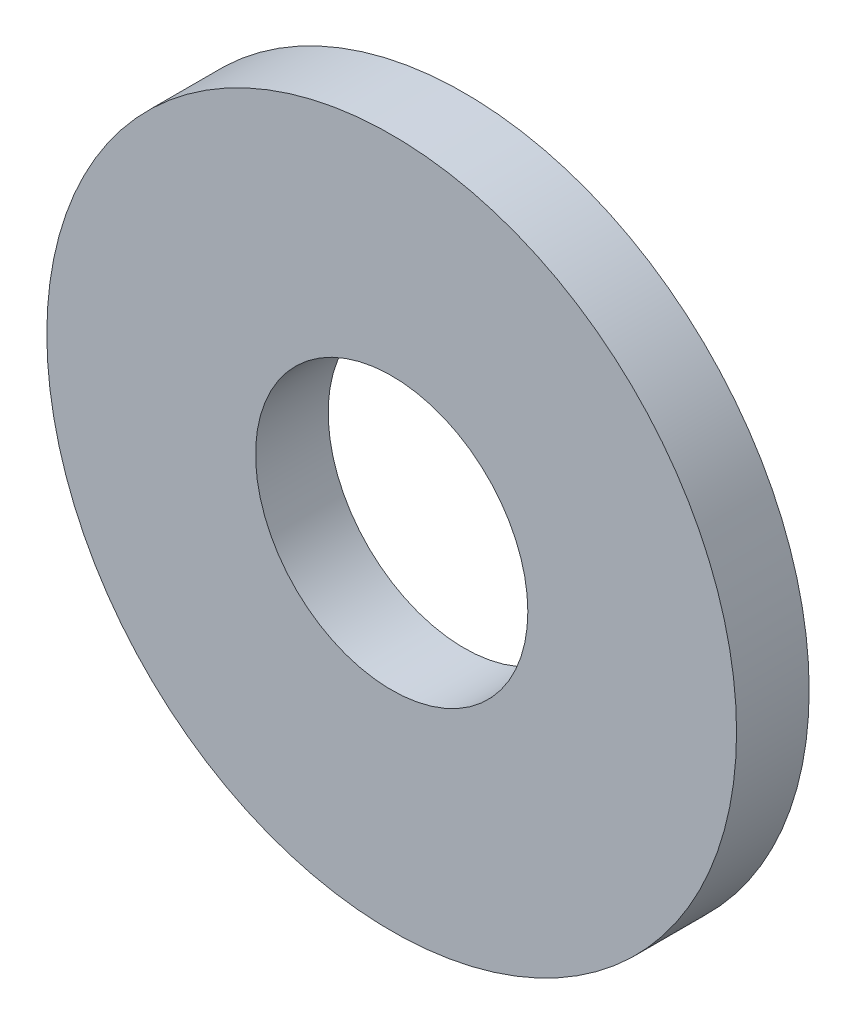
SolidWorks part; units mm, degrees
ref_plane "Front Plane" through (0, 0, 0) normal (0, 0, 1) x (1, 0, 0)
ref_plane "Top Plane" through (0, 0, 0) normal (0, 1, 0) x (1, 0, 0)
ref_plane "Right Plane" through (0, 0, 0) normal (1, 0, 0) x (0, 0, -1)
sketch "Sketch1" plane through (0, 0, 0) normal (0, 0, 1) x (1, 0, 0)
  line L0 (-4.826, 0) -> (4.826, 0) construction
  line L1 (-1.905, 0) -> (1.905, 0) construction
  circle A0 centre (0, 0) radius 1.905 construction
  circle A1 centre (0, 0) radius 4.826 construction
  point P8 (0, 0)
  point P9 (0, 4.826)
  point P11 (1.905, 0)
  dimension "ID" = 3.81
  dimension "OD" = 9.652
sketch "Sketch2" plane through (0, 0, 0) normal (1, 0, 0) x (0, 0, -1)
  line L0 (-0.508, 4.826) -> (0.508, 4.826) construction
  point P2 (0, 4.826)
  dimension "TH" = 1.016
sketch "Sketch3" plane through (0, 0, 0) normal (0, 0, 1) x (1, 0, 0)
  circle A0 centre (0, 0) radius 1.905
  circle A1 centre (0, 0) radius 4.826
extrude "Boss-Extrude1" add sketch "Sketch3" along normal up to vertex (0.508 mm away) and the other way up to vertex (0.508 mm away) up to point (0, 4.826, 0.508) other way up to point (0, 4.826, -0.508)
ref_axis "Center Axis 1" through (0, 0, 0.508) along (0, 0, -1)
